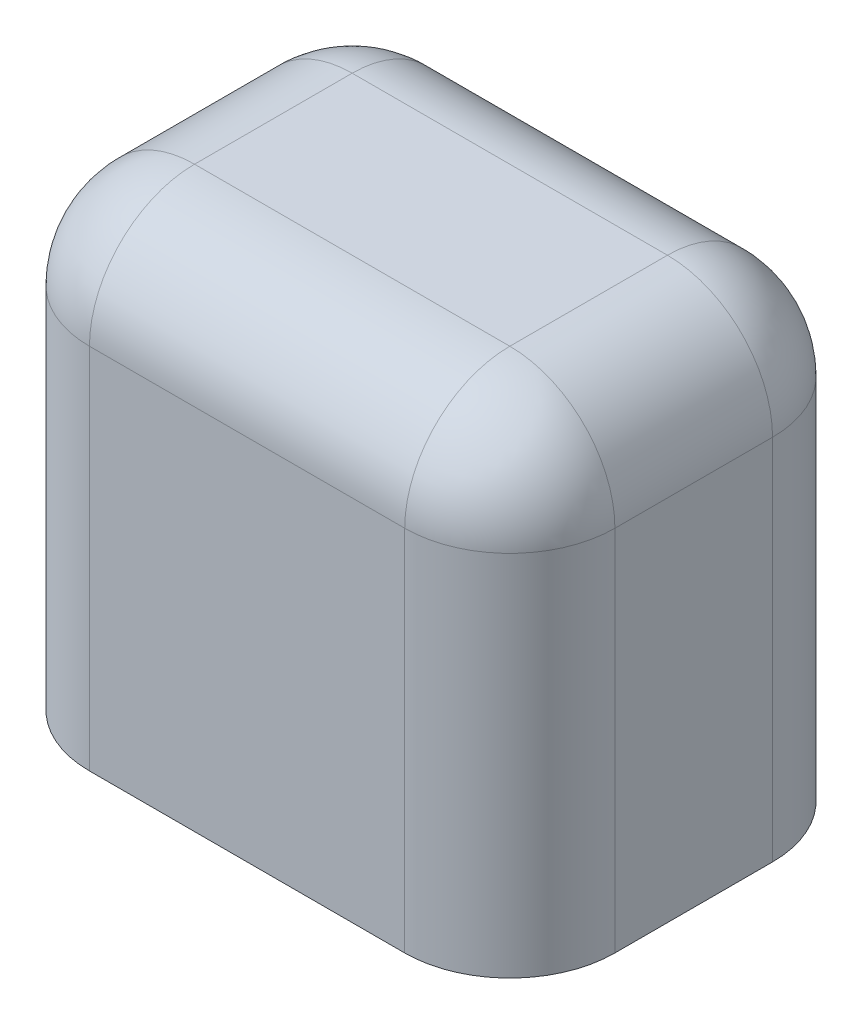
SolidWorks part; units mm, degrees
ref_plane "Alzado" through (0, 0, 0) normal (0, 0, 1) x (1, 0, 0)
ref_plane "Planta" through (0, 0, 0) normal (0, 1, 0) x (1, 0, 0)
ref_plane "Vista lateral" through (0, 0, 0) normal (1, 0, 0) x (0, 0, -1)
sketch "Croquis1" plane through (0, 0, 0) normal (0, 1, 0) x (1, 0, 0)
  line L1 (-15, 17.5) -> (15, 17.5)
  line L2 (-25, 7.5) -> (-25, -7.5)
  line L3 (-15, -17.5) -> (15, -17.5)
  line L4 (25, 7.5) -> (25, -7.5)
  line L5 (-25, 17.5) -> (25, -17.5) construction
  line L6 (-25, -17.5) -> (25, 17.5) construction
  arc A0 (15, 17.5) -> (25, 7.5) centre (15, 7.5) cw
  arc A1 (15, -17.5) -> (25, -7.5) centre (15, -7.5) ccw
  arc A2 (-25, -7.5) -> (-15, -17.5) centre (-15, -7.5) ccw
  arc A3 (-15, 17.5) -> (-25, 7.5) centre (-15, 7.5) ccw
  point P0 (0, 0)
  dimension "D3" = 10
  dimension "D1" = 50
  dimension "D2" = 35
extrude "Saliente-Extruir2" add sketch "Croquis1" along normal blind 45
fillet "Redondeo2" radius 10 8 edges at (-22.0711, 45, 14.5711) (-25, 45, 0) (-22.0711, 45, -14.5711) (0, 45, -17.5) (22.0711, 45, -14.5711) (25, 45, 0) (22.0711, 45, 14.5711) (0, 45, 17.5)
shell "Vaciado1" thickness 1.95 removed face at (0, 0, 0)
